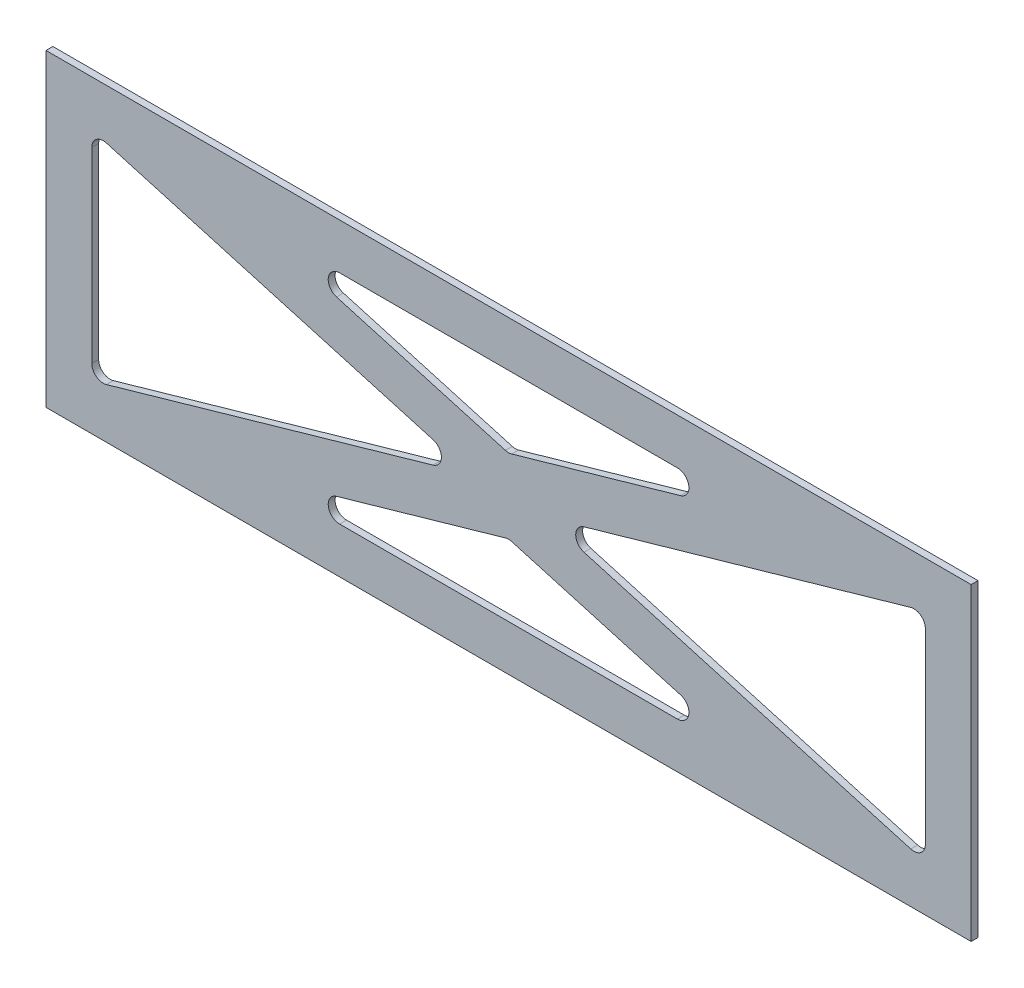
SolidWorks part; units mm, degrees
ref_plane "Front Plane" through (0, 0, 0) normal (0, 0, 1) x (1, 0, 0)
ref_plane "Top Plane" through (0, 0, 0) normal (0, 1, 0) x (1, 0, 0)
ref_plane "Right Plane" through (0, 0, 0) normal (1, 0, 0) x (0, 0, -1)
sketch "Sketch1" plane through (0, 0, 152) normal (0, 0, 1) x (1, 0, 0)
  line L1 (-67.5, 68) -> (336.5, 68)
  line L2 (-67.5, 68) -> (-67.5, -67)
  line L3 (-67.5, -67) -> (336.5, -67)
  line L4 (336.5, 68) -> (336.5, -67)
  line L6 (-47.5, -40.3667) -> (-47.5, 41.3667)
  line L7 (-41.1232, 46.1734) -> (101.5473, 5.3067)
  line L9 (-65.5, -84) -> (-65.5, 66) construction
  line L12 (334.5, -62) -> (-65.5, -62) construction
  line L13 (334.5, 63) -> (334.5, -62) construction
  line L14 (-65.5, -62) -> (-65.5, 63) construction
  line L15 (-65.5, 63) -> (334.5, 63) construction
  line L18 (208.2566, 48) -> (60.7434, 48)
  line L19 (101.5473, -4.3067) -> (-41.1232, -45.1734)
  line L20 (59.3666, 38.1933) -> (133.1232, 17.0664)
  line L21 (135.8768, 17.0664) -> (209.6334, 38.1933)
  line L22 (334.5, -49) -> (334.5, 31) construction
  line L23 (310.1232, 46.1734) -> (167.4527, 5.3067)
  line L24 (316.5, -40.3667) -> (316.5, 41.3667)
  line L25 (167.4527, -4.3067) -> (310.1232, -45.1734)
  line L26 (-65.5, 0.5) -> (334.5, 0.5) construction
  line L27 (59.3666, -37.1933) -> (133.1232, -16.0664)
  line L28 (208.2566, -47) -> (60.7434, -47)
  line L29 (135.8768, -16.0664) -> (209.6334, -37.1933)
  line L30 (134.5, 16.672) -> (134.5, -15.672) construction
  line L31 (118.328, 0.5) -> (150.672, 0.5) construction
  line L32 (134.5, 16.672) -> (134.5, -15.672) construction
  line L41 (234.5, -62) -> (-65.5, -62) construction
  line L42 (234.5, 63) -> (-65.5, 63) construction
  arc A0 (-41.1232, -45.1734) -> (-47.5, -40.3667) centre (-42.5, -40.3667) cw
  arc A1 (101.5473, -4.3067) -> (101.5473, 5.3067) centre (100.1704, 0.5) ccw
  arc A2 (-41.1232, 46.1734) -> (-47.5, 41.3667) centre (-42.5, 41.3667) ccw
  arc A3 (209.6334, -37.1933) -> (208.2566, -47) centre (208.2566, -42) cw
  arc A4 (59.3666, -37.1933) -> (60.7434, -47) centre (60.7434, -42) ccw
  arc A5 (133.1232, -16.0664) -> (135.8768, -16.0664) centre (134.5, -20.8731) cw
  arc A6 (167.4527, 5.3067) -> (167.4527, -4.3067) centre (168.8296, 0.5) ccw
  arc A7 (310.1232, -45.1734) -> (316.5, -40.3667) centre (311.5, -40.3667) ccw
  arc A8 (316.5, 41.3667) -> (310.1232, 46.1734) centre (311.5, 41.3667) ccw
  arc A9 (59.3666, 38.1933) -> (60.7434, 48) centre (60.7434, 43) cw
  arc A10 (209.6334, 38.1933) -> (208.2566, 48) centre (208.2566, 43) ccw
  arc A11 (135.8768, 17.0664) -> (133.1232, 17.0664) centre (134.5, 21.8731) cw
  point P14 (134.5, 0.5)
  point P15 (134.5, 0.5)
  point P32 (-47.5, 48)
  point P35 (243.8697, -47)
  point P38 (25.1303, -47)
  point P51 (25.1303, 48)
  point P54 (243.8697, 48)
  dimension "D9" = 5
  dimension "D10" = 5
  dimension "D1" = 2
  dimension "D2" = 2
  dimension "D3" = 5
  dimension "D4" = 5
  dimension "D5" = 20
  dimension "D6" = 20
  dimension "D7" = 20
  dimension "D8" = 20
  dimension "D11" = 20
extrude "Boss-Extrude1" add sketch "Sketch1" along normal blind 3
